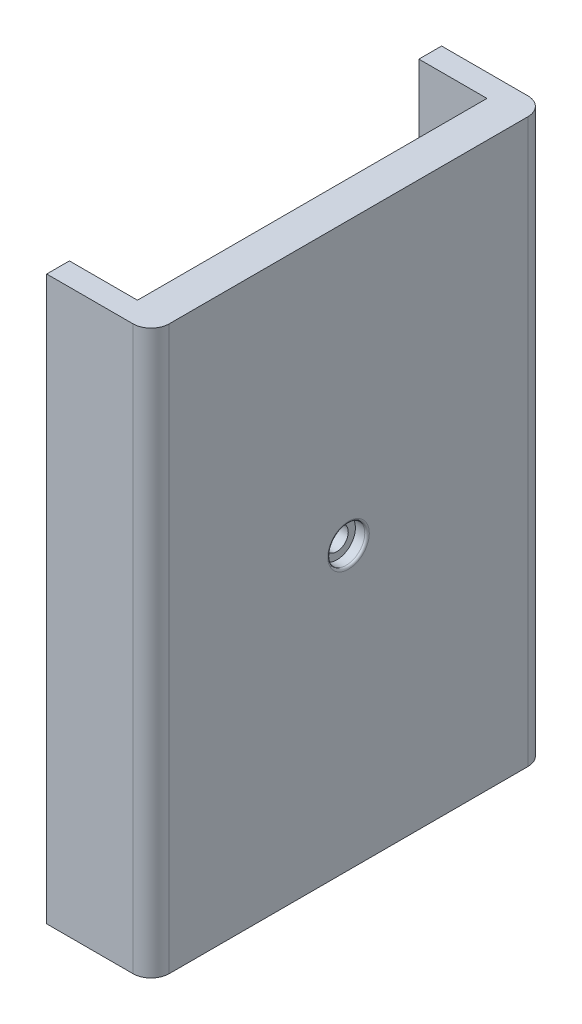
SolidWorks part; units mm, degrees
note: The reader was unsure of these and kept them because the rebuilt part matched: shared geometry of "Sketch12<6>".
other "Markup1"
sketch "Sketch9" plane through (-25.745, 62.7203, -36.576) normal (-0.5706, 0.1284, -0.8112) x (-0.8147, 0.0363, 0.5788)
ref_plane "Front Plane" through (0, 0, 0) normal (0, 0, 1) x (1, 0, 0)
ref_plane "Top Plane" through (0, 0, 0) normal (0, 1, 0) x (1, 0, 0)
ref_plane "Right Plane" through (0, 0, 0) normal (1, 0, 0) x (0, 0, -1)
sketch "Sketch1" plane through (0, 0, 0) normal (0, 0, 1) x (1, 0, 0)
  line L0 (8.255, 0) -> (-8.255, 0) construction
  line L1 (20.255, 0) -> (-20.255, 0) construction
  line L2 (8.255, 0) -> (8.255, 18.25)
  line L3 (8.255, 18.25) -> (20.255, 18.25)
  line L4 (20.255, 18.25) -> (20.255, 0)
  line L5 (8.255, 0) -> (20.255, 0)
  point P4 (0, 0)
  point P8 (0, 0)
  dimension "D1" = 16.51
  dimension "D2" = 12
  dimension "D3" = 18.25
revolve "Revolve1" add sketch "Sketch1" angle 360 about L5
sketch "Sketch2" plane through (8.255, 0, 0) normal (-1, 0, 0) x (0, 0, 1)
  circle A0 centre (0, 0) radius 3.7145
  dimension "D1" = 7.429
extrude "Cut-Extrude1" cut sketch "Sketch2" against normal blind 8.5725
sketch "Sketch3" plane through (20.255, 0, 0) normal (1, 0, 0) x (0, 0, -1)
  line L1 (13.175, -55) -> (-13.175, -55) construction
  line L2 (13.175, -55) -> (13.175, 55) construction
  line L3 (13.175, 55) -> (-13.175, 55) construction
  line L4 (-13.175, -55) -> (-13.175, 55) construction
  line L5 (13.175, -55) -> (-13.175, 55) construction
  line L6 (13.175, 55) -> (-13.175, -55) construction
  line L14 (6.6, 0) -> (-6.6, 0) construction
  line L15 (13.175, -55) -> (-13.175, 55) construction
  line L16 (13.175, 55) -> (-13.175, -55) construction
  line L17 (13.175, 55) -> (-13.175, 55) construction
  line L28 (-36.576, 0) -> (36.576, 0) construction
  line L33 (43.5, -62) -> (-43.5, -62)
  line L34 (43.5, -62) -> (43.5, 62)
  line L35 (43.5, 62) -> (-43.5, 62)
  line L36 (-43.5, -62) -> (-43.5, 62)
  line L37 (43.5, -62) -> (-43.5, 62) construction
  line L38 (43.5, 62) -> (-43.5, -62) construction
  point P0 (0, 0)
  point P11 (0, 0)
  point P12 (0, 0)
  dimension "D3" = 124
  dimension "D4" = 87
  dimension "D9" = 110
  dimension "D1" = 73.152
  dimension "D2" = 26.35
extrude "Boss-Extrude1" add sketch "Sketch3" along normal blind 8 separate body
sketch "Sketch4" plane through (20.255, 0, 0) normal (-1, 0, 0) x (0, 0, 1)
  line L0 (-19.575, 55) -> (-6.775, 55) construction
  line L1 (13.175, -55) -> (-13.175, -55) construction
  line L2 (13.175, -55) -> (13.175, 55) construction
  line L3 (13.175, 55) -> (-13.175, 55) construction
  line L4 (-13.175, -55) -> (-13.175, 55) construction
  line L5 (13.175, -55) -> (-13.175, 55) construction
  line L6 (13.175, 55) -> (-13.175, -55) construction
  circle A0 centre (-13.175, 55) radius 4.75
  circle A1 centre (13.175, -55) radius 4.75
  circle A2 centre (13.175, 55) radius 4.75
  circle A3 centre (-13.175, -55) radius 4.75
  circle A5 centre (-13.175, 55) radius 6.4
  circle A6 centre (13.175, 55) radius 6.4
  circle A7 centre (13.175, -55) radius 6.4
  circle A8 centre (-13.175, -55) radius 6.4
  point P6 (0, 0)
  dimension "D1" = 9.5
  dimension "D2" = 12.8
  dimension "D3" = 26.35
  dimension "D4" = 110
sketch "Sketch5" plane through (8.255, 0, 0) normal (-1, 0, 0) x (0, 0, 1)
  circle A0 centre (0, 0) radius 18.25
  dimension "D1" = 36.5
fillet "Fillet1" radius 4 2 edges at (28.255, 0, -43.5) (28.255, 0, 43.5)
sketch "Sketch6" plane through (8.255, 0, 0) normal (-1, 0, 0) x (0, 0, 1)
  circle A2 centre (0, 0) radius 13.15
  dimension "D1" = 26.3
extrude "Cut-Extrude2" cut sketch "Sketch6" against normal blind 12
ref_plane "Plane1" through (0, 0, 38) normal (0, 0, 1) x (1, 0, 0)
ref_plane "Plane2" through (19.255, 0, 0) normal (-1, 0, 0) x (0, 0, 1)
sketch "Sketch12" plane through (28.255, 0, 0) normal (1, 0, 0) x (0, 0, -1)
  circle A0 centre (0, 0) radius 4.075
  circle A1 centre (0, 0) radius 2.5
  dimension "D1" = 8.15
  dimension "D2" = 5
extrude "Cut-Extrude6" cut sketch "Sketch12" against normal blind 2.56 contours A0
extrude "Cut-Extrude7" cut sketch "Sketch12<6>" against normal up to surface (8 mm away) contours A1 up to face at (20.255, 0, 0)
sketch "Sketch12<6>" plane through (28.255, 0, 0) normal (1, 0, 0) x (0, 0, -1) same geometry as "Sketch12"
fillet "Fillet2" radius 0.5 1 edges at (28.255, 4.075, 0)
combine bodies "Combine1" operation type add bodies to combine 124 127
fillet "Fillet3" [suppressed] radius 2
sketch "Sketch14" plane through (0, -62, 0) normal (0, -1, 0) x (1, 0, 0)
  line L0 (28.255, 0) -> (-41.715, 0) construction
  line L1 (28.255, -39.5) -> (28.255, 39.5) construction
  line L3 (18.52, -12.75) -> (-31.98, -12.75) construction
  line L4 (18.52, -12.75) -> (18.52, 12.75) construction
  line L5 (18.52, 12.75) -> (-31.98, 12.75) construction
  line L6 (-31.98, -12.75) -> (-31.98, 12.75) construction
  line L7 (18.52, -12.75) -> (-31.98, 12.75) construction
  line L8 (18.52, 12.75) -> (-31.98, -12.75) construction
  circle A0 centre (18.52, 12.75) radius 3.7138
  circle A1 centre (18.52, -12.75) radius 3.7138
  point P6 (-6.73, 0)
  dimension "D4" = 7.4275
  dimension "D1" = 69.97
  dimension "D2" = 50.5
  dimension "D3" = 25.5
extrude "Cut-Extrude8" [suppressed] cut sketch "Sketch14" against normal blind 9.5
sketch "Sketch15" plane through (20.255, 0, 0) normal (-1, 0, 0) x (0, 0, 1)
  line L0 (-43.5, -62) -> (43.5, -62) construction
  line L1 (-43.5, 62) -> (-38.5, 62)
  line L2 (-43.5, 62) -> (-43.5, -62)
  line L3 (-43.5, -62) -> (-38.5, -62)
  line L4 (-38.5, 62) -> (-38.5, -62)
  line L6 (43.5, 62) -> (38.5, 62)
  line L7 (43.5, 62) -> (43.5, -62)
  line L8 (43.5, -62) -> (38.5, -62)
  line L9 (38.5, 62) -> (38.5, -62)
  dimension "D1" = 5
extrude "Boss-Extrude2" add sketch "Sketch15" along normal blind 15
